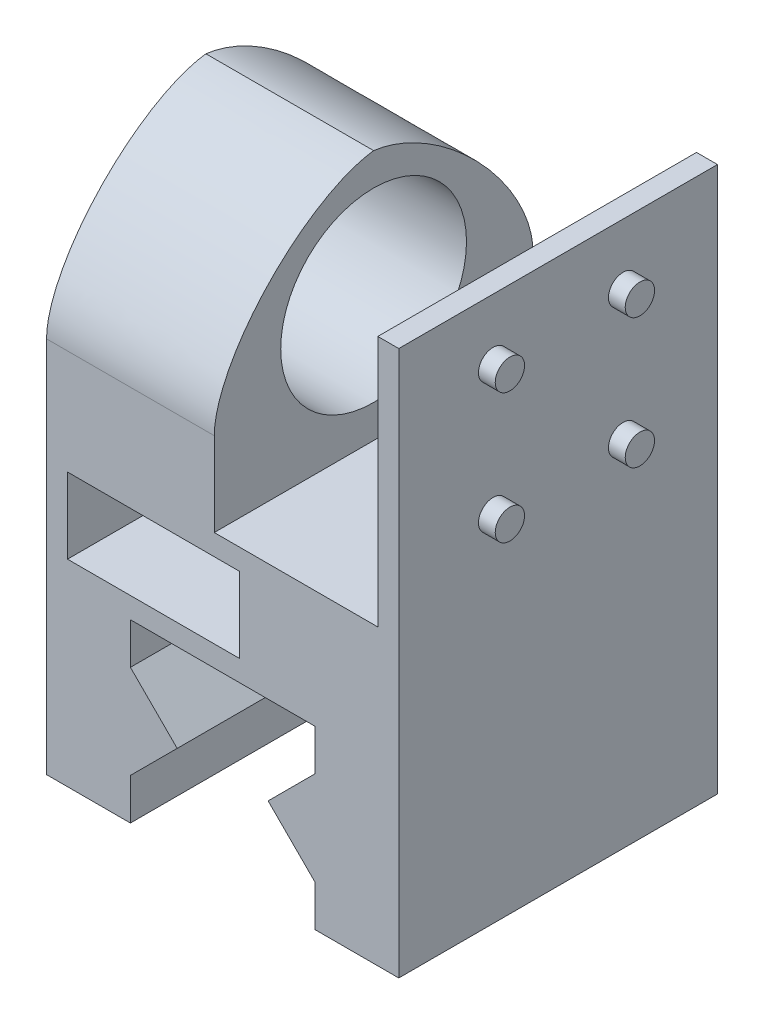
SolidWorks part; units mm, degrees
ref_plane "Front Plane" through (0, 0, 0) normal (0, 0, 1) x (1, 0, 0)
ref_plane "Top Plane" through (0, 0, 0) normal (0, 1, 0) x (1, 0, 0)
ref_plane "Right Plane" through (0, 0, 0) normal (1, 0, 0) x (0, 0, -1)
sketch "Sketch1" plane through (0, 0, 0) normal (0, 0, 1) x (1, 0, 0)
  line L0 (-11, 0) -> (11, 0)
  line L1 (11, 0) -> (11, -4.92)
  line L2 (11, -4.92) -> (5.42, -10.5)
  line L3 (5.42, -10.5) -> (11, -10.5) construction
  line L4 (11, -16.08) -> (5.42, -10.5)
  line L5 (11, -16.08) -> (11, -21)
  line L6 (0, 0) -> (0, -50000) construction
  line L7 (11, -21) -> (21, -21)
  line L8 (21, -21) -> (21, 14)
  line L9 (21, 14) -> (-21, 14)
  line L10 (-5.42, -10.5) -> (-11, -10.5) construction
  line L11 (-21, -21) -> (-21, 14)
  line L12 (-11, -21) -> (-21, -21)
  line L13 (-11, -16.08) -> (-11, -21)
  line L14 (-11, -16.08) -> (-5.42, -10.5)
  line L15 (-11, -4.92) -> (-5.42, -10.5)
  line L16 (-11, 0) -> (-11, -4.92)
  line L18 (-18.5, 11.5) -> (2, 11.5)
  line L19 (-18.5, 11.5) -> (-18.5, 2.5)
  line L20 (-18.5, 2.5) -> (2, 2.5)
  line L21 (2, 11.5) -> (2, 2.5)
  point P16 (0, 14)
  point P21 (0, 0)
  dimension "D1" = 11
  dimension "D2" = 4.92
  dimension "D3" = 7.8913
  dimension "D4" = 45
  dimension "D5" = 4.92
  dimension "D6" = 10
  dimension "D7" = 35
  dimension "D8" = 2.5
  dimension "D9" = 2.5
  dimension "D10" = 19
  dimension "D11" = 2.5
extrude "Boss-Extrude1" add sketch "Sketch1" along normal mid plane 38
sketch "Sketch2" plane through (0, 14, 0) normal (0, 1, 0) x (1, 0, 0)
  line L0 (21, -19) -> (-21, -19) construction
  line L1 (-21, 19) -> (-1, 19)
  line L2 (-21, 19) -> (-21, -19)
  line L3 (-21, -19) -> (-1, -19)
  line L4 (-1, 19) -> (-1, -19)
  dimension "D1" = 20
extrude "Boss-Extrude2" add sketch "Sketch2" along normal blind 30
fillet "Fillet2" radius 20 2 edges at (-11, 44, -19) (-11, 44, 19) conic rho 0.3
sketch "Sketch7" plane through (0, 14, 0) normal (0, 1, 0) x (1, 0, 0)
  line L0 (21, 19) -> (-1, 19) construction
  line L1 (18.5, 19) -> (21, 19)
  line L2 (18.5, 19) -> (18.5, -19)
  line L3 (18.5, -19) -> (21, -19)
  line L4 (21, 19) -> (21, -19)
  dimension "D1" = 2.5
extrude "Boss-Extrude6" add sketch "Sketch7" along normal blind 30
sketch "Sketch3" plane through (-21, 0, 0) normal (-1, 0, 0) x (0, 0, 1)
  line L0 (0, 0) -> (0, 44) construction
  circle A0 centre (0, 29) radius 11.075
  dimension "D1" = 22.15
  dimension "D2" = 29
extrude "Cut-Extrude1" cut sketch "Sketch3" against normal blind 31 and the other way through all
sketch "Sketch8" plane through (21, 0, 0) normal (1, 0, 0) x (0, 0, -1)
  line L0 (-19, 44) -> (19, 44) construction
  circle A0 centre (0, 29) radius 4
  dimension "D1" = 15
  dimension "D2" = 8
extrude "Cut-Extrude4" cut sketch "Sketch8" against normal blind 20
sketch "Sketch9" plane through (21, 0, 0) normal (1, 0, 0) x (0, 0, -1)
  line L0 (-19, 44) -> (19, 44) construction
  line L1 (-19, -21) -> (-19, 44) construction
  line L2 (19, -21) -> (19, 44) construction
  circle A0 centre (-7.75, 36.75) radius 1.75
  circle A1 centre (7.75, 36.75) radius 1.75
  circle A2 centre (-7.75, 21.25) radius 1.75
  circle A3 centre (7.75, 21.25) radius 1.75
  dimension "D1" = 3.5
  dimension "D2" = 3.5
  dimension "D3" = 3.5
  dimension "D4" = 3.5
  dimension "D5" = 7.25
  dimension "D6" = 11.25
  dimension "D7" = 11.25
  dimension "D8" = 15.5
extrude "Boss-Extrude7" add sketch "Sketch9" along normal blind 2
ref_axis "Axis1" through (-43.101, 29, 0) along (-1, 0, 0)
sketch "Sketch5" plane through (0, 14, 0) normal (0, 1, 0) x (1, 0, 0)
  line L0 (18.5, 19) -> (-1, 19) construction
  line L1 (18.5, 19) -> (21, 19)
  line L2 (18.5, 19) -> (18.5, -19)
  line L3 (18.5, -19) -> (21, -19)
  line L4 (21, 19) -> (21, -19)
  line L5 (18.5, -19) -> (-1, -19) construction
  line L6 (21, -19) -> (21, 19) construction
  dimension "D1" = 2.5
extrude "Boss-Extrude3" add sketch "Sketch5" along normal blind 30
